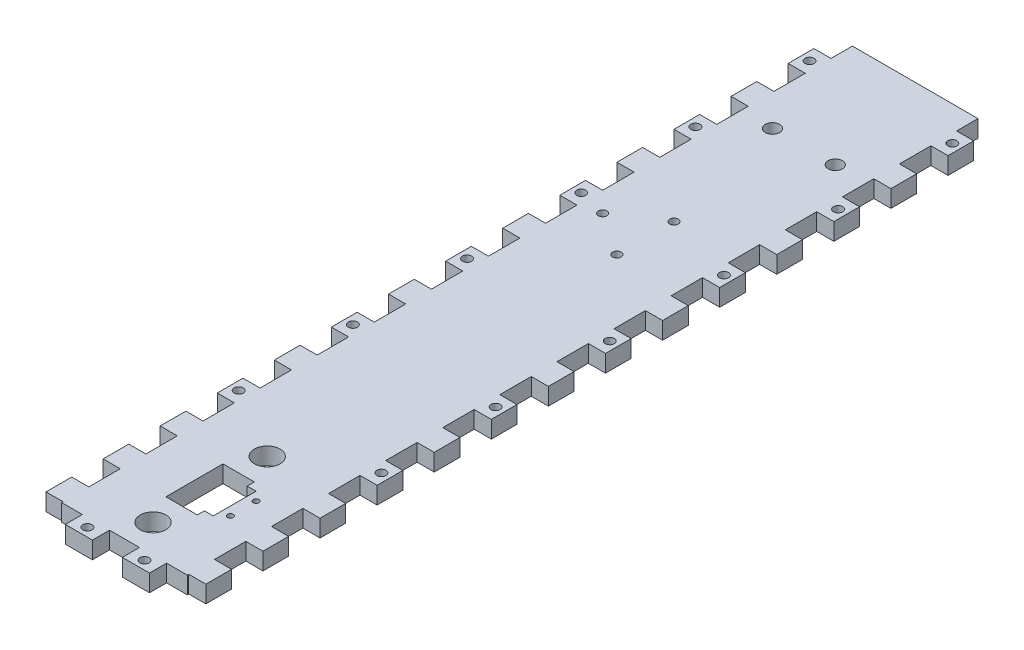
SolidWorks part; units mm, degrees
ref_plane "Plan de face" through (0, 0, 0) normal (0, 0, 1) x (1, 0, 0)
ref_plane "Plan de dessus" through (0, 0, 0) normal (0, 1, 0) x (1, 0, 0)
ref_plane "Plan de droite" through (0, 0, 0) normal (1, 0, 0) x (0, 0, -1)
sketch "Sketch1" plane through (0, 0, 0) normal (0, 0, 1) x (1, 0, 0)
  line L1 (-30.0201, 10.5217) -> (13.9799, 10.5217)
  line L2 (-30.0201, 10.5217) -> (-30.0201, 4.5217)
  line L3 (-30.0201, 4.5217) -> (13.9799, 4.5217)
  line L4 (13.9799, 10.5217) -> (13.9799, 4.5217)
  dimension "D1" = 44
  dimension "D2" = 6
extrude "Boss-Extrude1" add sketch "Sketch1" along normal blind 277
sketch "Sketch4" plane through (13.9799, 0, 0) normal (1, 0, 0) x (0, 0, -1)
  line L0 (-277, 10.5217) -> (0, 10.5217) construction
  line L1 (-276.5, 10.5217) -> (-267.5, 10.5217)
  line L2 (-276.5, 10.5217) -> (-276.5, 4.5217)
  line L3 (-276.5, 4.5217) -> (-267.5, 4.5217)
  line L4 (-267.5, 10.5217) -> (-267.5, 4.5217)
  line L5 (-277, 4.5217) -> (0, 4.5217) construction
  line L6 (-277, 4.5217) -> (-277, 10.5217) construction
  line L7 (-256.5, 10.5217) -> (-256.5, 4.5217)
  line L8 (-256.5, 10.5217) -> (-247.5, 10.5217)
  line L9 (-247.5, 10.5217) -> (-247.5, 4.5217)
  line L10 (-256.5, 4.5217) -> (-247.5, 4.5217)
  line L11 (-236.5, 10.5217) -> (-236.5, 4.5217)
  line L12 (-236.5, 10.5217) -> (-227.5, 10.5217)
  line L13 (-227.5, 10.5217) -> (-227.5, 4.5217)
  line L14 (-236.5, 4.5217) -> (-227.5, 4.5217)
  line L15 (-216.5, 10.5217) -> (-216.5, 4.5217)
  line L16 (-216.5, 10.5217) -> (-207.5, 10.5217)
  line L17 (-207.5, 10.5217) -> (-207.5, 4.5217)
  line L18 (-216.5, 4.5217) -> (-207.5, 4.5217)
  line L19 (-196.5, 10.5217) -> (-196.5, 4.5217)
  line L20 (-196.5, 10.5217) -> (-187.5, 10.5217)
  line L21 (-187.5, 10.5217) -> (-187.5, 4.5217)
  line L22 (-196.5, 4.5217) -> (-187.5, 4.5217)
  line L23 (-176.5, 10.5217) -> (-176.5, 4.5217)
  line L24 (-176.5, 10.5217) -> (-167.5, 10.5217)
  line L25 (-167.5, 10.5217) -> (-167.5, 4.5217)
  line L26 (-176.5, 4.5217) -> (-167.5, 4.5217)
  line L27 (-156.5, 10.5217) -> (-156.5, 4.5217)
  line L28 (-156.5, 10.5217) -> (-147.5, 10.5217)
  line L29 (-147.5, 10.5217) -> (-147.5, 4.5217)
  line L30 (-156.5, 4.5217) -> (-147.5, 4.5217)
  line L31 (-136.5, 10.5217) -> (-136.5, 4.5217)
  line L32 (-136.5, 10.5217) -> (-127.5, 10.5217)
  line L33 (-127.5, 10.5217) -> (-127.5, 4.5217)
  line L34 (-136.5, 4.5217) -> (-127.5, 4.5217)
  line L35 (-116.5, 10.5217) -> (-116.5, 4.5217)
  line L36 (-116.5, 10.5217) -> (-107.5, 10.5217)
  line L37 (-107.5, 10.5217) -> (-107.5, 4.5217)
  line L38 (-116.5, 4.5217) -> (-107.5, 4.5217)
  line L39 (-96.5, 10.5217) -> (-96.5, 4.5217)
  line L40 (-96.5, 10.5217) -> (-87.5, 10.5217)
  line L41 (-87.5, 10.5217) -> (-87.5, 4.5217)
  line L42 (-96.5, 4.5217) -> (-87.5, 4.5217)
  line L43 (-76.5, 10.5217) -> (-76.5, 4.5217)
  line L44 (-76.5, 10.5217) -> (-67.5, 10.5217)
  line L45 (-67.5, 10.5217) -> (-67.5, 4.5217)
  line L46 (-76.5, 4.5217) -> (-67.5, 4.5217)
  line L47 (-56.5, 10.5217) -> (-56.5, 4.5217)
  line L48 (-56.5, 10.5217) -> (-47.5, 10.5217)
  line L49 (-47.5, 10.5217) -> (-47.5, 4.5217)
  line L50 (-56.5, 4.5217) -> (-47.5, 4.5217)
  line L51 (-36.5, 10.5217) -> (-36.5, 4.5217)
  line L52 (-36.5, 10.5217) -> (-27.5, 10.5217)
  line L53 (-27.5, 10.5217) -> (-27.5, 4.5217)
  line L54 (-36.5, 4.5217) -> (-27.5, 4.5217)
  line L55 (-16.5, 10.5217) -> (-16.5, 4.5217)
  line L56 (-16.5, 10.5217) -> (-7.5, 10.5217)
  line L57 (-7.5, 10.5217) -> (-7.5, 4.5217)
  line L58 (-16.5, 4.5217) -> (-7.5, 4.5217)
  dimension "D1" = 0.5
  dimension "D2" = 9
  dimension "D3" = 14
extrude "Boss-Extrude2" add sketch "Sketch4" along normal blind 6
sketch "Sketch5" plane through (-30.0201, 0, 0) normal (-1, 0, 0) x (0, 0, 1)
  line L0 (277, 4.5217) -> (0, 4.5217) construction
  line L1 (276.5, 4.5217) -> (267.5, 4.5217)
  line L2 (276.5, 4.5217) -> (276.5, 10.5217)
  line L3 (276.5, 10.5217) -> (267.5, 10.5217)
  line L4 (267.5, 4.5217) -> (267.5, 10.5217)
  line L5 (277, 10.5217) -> (0, 10.5217) construction
  line L6 (277, 10.5217) -> (277, 4.5217) construction
  line L7 (256.5, 4.5217) -> (256.5, 10.5217)
  line L8 (256.5, 4.5217) -> (247.5, 4.5217)
  line L9 (247.5, 4.5217) -> (247.5, 10.5217)
  line L10 (256.5, 10.5217) -> (247.5, 10.5217)
  line L11 (236.5, 4.5217) -> (236.5, 10.5217)
  line L12 (236.5, 4.5217) -> (227.5, 4.5217)
  line L13 (227.5, 4.5217) -> (227.5, 10.5217)
  line L14 (236.5, 10.5217) -> (227.5, 10.5217)
  line L15 (216.5, 4.5217) -> (216.5, 10.5217)
  line L16 (216.5, 4.5217) -> (207.5, 4.5217)
  line L17 (207.5, 4.5217) -> (207.5, 10.5217)
  line L18 (216.5, 10.5217) -> (207.5, 10.5217)
  line L19 (196.5, 4.5217) -> (196.5, 10.5217)
  line L20 (196.5, 4.5217) -> (187.5, 4.5217)
  line L21 (187.5, 4.5217) -> (187.5, 10.5217)
  line L22 (196.5, 10.5217) -> (187.5, 10.5217)
  line L23 (176.5, 4.5217) -> (176.5, 10.5217)
  line L24 (176.5, 4.5217) -> (167.5, 4.5217)
  line L25 (167.5, 4.5217) -> (167.5, 10.5217)
  line L26 (176.5, 10.5217) -> (167.5, 10.5217)
  line L27 (156.5, 4.5217) -> (156.5, 10.5217)
  line L28 (156.5, 4.5217) -> (147.5, 4.5217)
  line L29 (147.5, 4.5217) -> (147.5, 10.5217)
  line L30 (156.5, 10.5217) -> (147.5, 10.5217)
  line L31 (136.5, 4.5217) -> (136.5, 10.5217)
  line L32 (136.5, 4.5217) -> (127.5, 4.5217)
  line L33 (127.5, 4.5217) -> (127.5, 10.5217)
  line L34 (136.5, 10.5217) -> (127.5, 10.5217)
  line L35 (116.5, 4.5217) -> (116.5, 10.5217)
  line L36 (116.5, 4.5217) -> (107.5, 4.5217)
  line L37 (107.5, 4.5217) -> (107.5, 10.5217)
  line L38 (116.5, 10.5217) -> (107.5, 10.5217)
  line L39 (96.5, 4.5217) -> (96.5, 10.5217)
  line L40 (96.5, 4.5217) -> (87.5, 4.5217)
  line L41 (87.5, 4.5217) -> (87.5, 10.5217)
  line L42 (96.5, 10.5217) -> (87.5, 10.5217)
  line L43 (76.5, 4.5217) -> (76.5, 10.5217)
  line L44 (76.5, 4.5217) -> (67.5, 4.5217)
  line L45 (67.5, 4.5217) -> (67.5, 10.5217)
  line L46 (76.5, 10.5217) -> (67.5, 10.5217)
  line L47 (56.5, 4.5217) -> (56.5, 10.5217)
  line L48 (56.5, 4.5217) -> (47.5, 4.5217)
  line L49 (47.5, 4.5217) -> (47.5, 10.5217)
  line L50 (56.5, 10.5217) -> (47.5, 10.5217)
  line L51 (36.5, 4.5217) -> (36.5, 10.5217)
  line L52 (36.5, 4.5217) -> (27.5, 4.5217)
  line L53 (27.5, 4.5217) -> (27.5, 10.5217)
  line L54 (36.5, 10.5217) -> (27.5, 10.5217)
  line L55 (16.5, 4.5217) -> (16.5, 10.5217)
  line L56 (16.5, 4.5217) -> (7.5, 4.5217)
  line L57 (7.5, 4.5217) -> (7.5, 10.5217)
  line L58 (16.5, 10.5217) -> (7.5, 10.5217)
  dimension "D1" = 0.5
  dimension "D2" = 9
  dimension "D3" = 14
extrude "Boss-Extrude3" add sketch "Sketch5" along normal blind 6
sketch "Sketch6" plane through (0, 0, 277) normal (0, 0, 1) x (1, 0, 0)
  line L0 (13.9799, 10.5217) -> (-30.0201, 10.5217) construction
  line L1 (-22.7701, 10.5217) -> (-13.2701, 10.5217)
  line L2 (-22.7701, 10.5217) -> (-22.7701, 4.5217)
  line L3 (-22.7701, 4.5217) -> (-13.2701, 4.5217)
  line L4 (-13.2701, 10.5217) -> (-13.2701, 4.5217)
  line L5 (-30.0201, 4.5217) -> (13.9799, 4.5217) construction
  line L6 (-30.0201, 4.5217) -> (-30.0201, 10.5217) construction
  line L7 (-2.7701, 10.5217) -> (-2.7701, 4.5217)
  line L8 (-2.7701, 10.5217) -> (6.7299, 10.5217)
  line L9 (6.7299, 10.5217) -> (6.7299, 4.5217)
  line L10 (-2.7701, 4.5217) -> (6.7299, 4.5217)
  dimension "D1" = 7.25
  dimension "D2" = 9.5
  dimension "D3" = 2
extrude "Boss-Extrude4" add sketch "Sketch6" along normal blind 6
sketch "Sketch7" plane through (0, 4.5217, 0) normal (0, -1, 0) x (1, 0, 0)
  line L0 (-8.0201, 277) -> (-8.0201, 0) construction
  line L2 (-30.0201, 0) -> (13.9799, 0) construction
  line L3 (19.9799, 256.5) -> (19.9799, 247.5) construction
  line L6 (19.9799, 256.5) -> (13.9799, 256.5) construction
  circle A0 centre (16.9799, 252) radius 1.6
  circle A1 centre (-33.0201, 252) radius 1.6
  circle A2 centre (-33.0201, 212) radius 1.6
  circle A3 centre (16.9799, 212) radius 1.6
  circle A4 centre (-33.0201, 172) radius 1.6
  circle A5 centre (16.9799, 172) radius 1.6
  circle A6 centre (-33.0201, 132) radius 1.6
  circle A7 centre (16.9799, 132) radius 1.6
  circle A8 centre (-33.0201, 92) radius 1.6
  circle A9 centre (16.9799, 92) radius 1.6
  circle A10 centre (-33.0201, 52) radius 1.6
  circle A11 centre (16.9799, 52) radius 1.6
  circle A12 centre (-33.0201, 12) radius 1.6
  circle A13 centre (16.9799, 12) radius 1.6
  point P6 (19.9799, 252)
  point P15 (16.9799, 256.5)
  dimension "D1" = 7
  dimension "D3" = 3.2
extrude "Cut-Extrude1" cut sketch "Sketch7" against normal through all
sketch "Sketch8" plane through (0, 4.5217, 0) normal (0, -1, 0) x (1, 0, 0)
  line L0 (-8.0201, 0) -> (-8.0201, 54.5316) construction
  line L1 (-30.0201, 0) -> (13.9799, 0) construction
  circle A0 centre (-19.0201, 39) radius 2.5
  circle A1 centre (2.9799, 39) radius 2.5
  dimension "D1" = 5
  dimension "D2" = 11
  dimension "D3" = 39
extrude "Cut-Extrude2" cut sketch "Sketch8" against normal blind 12
sketch "Sketch9" plane through (0, 4.5217, 0) normal (0, -1, 0) x (-1, 0, 0)
  line L1 (2.7701, -283) -> (-6.7299, -283) construction
  line L2 (22.7701, -283) -> (13.2701, -283) construction
  line L3 (13.2701, -283) -> (13.2701, -277) construction
  line L4 (-6.7299, -283) -> (-6.7299, -277) construction
  circle A0 centre (18.0201, -280) radius 1.6
  circle A1 centre (-1.9799, -280) radius 1.6
  point P2 (-1.9799, -283)
  point P6 (18.0201, -283)
  point P14 (13.2701, -280)
  point P17 (-6.7299, -280)
  dimension "D1" = 3.2
  dimension "D2" = 3.2
extrude "Cut-Extrude3" cut sketch "Sketch9" against normal blind 12
sketch "Sketch11" plane through (0, 4.5217, 0) normal (0, -1, 0) x (1, 0, 0)
  line L0 (6.7299, 277) -> (13.9799, 277) construction
  line L2 (-13.5201, 257) -> (-2.5201, 257)
  line L3 (-13.5201, 257) -> (-13.5201, 237)
  line L4 (-13.5201, 237) -> (-2.5201, 237)
  line L5 (-2.5201, 257) -> (-2.5201, 237)
  line L6 (-2.5201, 254.5) -> (0.5799, 254.5)
  line L7 (-2.5201, 254.5) -> (-2.5201, 239.5)
  line L8 (-2.5201, 239.5) -> (0.5799, 239.5)
  line L9 (0.5799, 254.5) -> (0.5799, 239.5)
  line L10 (-13.2701, 277) -> (-2.7701, 277) construction
  circle A0 centre (-8.0201, 267) radius 4.5
  circle A1 centre (-8.0201, 227) radius 4.5
  circle A2 centre (3.5799, 251.5) radius 1
  circle A3 centre (3.5799, 242.5) radius 1
  point P11 (-8.0201, 257)
  point P16 (-2.5201, 247)
  point P17 (-2.5201, 247)
  point P24 (-8.0201, 277)
  dimension "D1" = 9
  dimension "D2" = 9
  dimension "D10" = 2
  dimension "D11" = 2
  dimension "D3" = 40
  dimension "D4" = 10
  dimension "D5" = 11
  dimension "D6" = 10
  dimension "D7" = 10
  dimension "D8" = 3.1
  dimension "D9" = 15
  dimension "D12" = 3
  dimension "D13" = 3
  dimension "D14" = 3
extrude "Cut-Extrude4" cut sketch "Sketch11" against normal through all contours L5 L2 L3 L4 | L9 L6 L5 L8 | A0 | A1 | A2 | A3 region at (-8.0201, 4.5217, 247) region at (-0.9701, 4.5217, 247) region at (-8.0201, 4.5217, 267) region at (-8.0201, 4.5217, 227) region at (3.5799, 4.5217, 251.5) region at (3.5799, 4.5217, 242.5)
extrude "Boss-Extrude5" add sketch "Sketch7<2>" against normal through all contours A1 | A0 region at (16.9799, 4.5217, 252) region at (-33.0201, 4.5217, 252)
sketch "Sketch7<2>" plane through (0, 4.5217, 0) normal (0, -1, 0) x (1, 0, 0) same geometry as "Sketch7"
sketch "Sketch12" plane through (0, 10.5217, 0) normal (0, 1, 0) x (1, 0, 0)
  line L1 (13.9799, 0) -> (-30.0201, 0) construction
  line L2 (-13.2701, -277) -> (-2.7701, -277) construction
  circle A0 centre (-8.0201, -104.5) radius 1.5
  circle A1 centre (-8.0201, -84.5) radius 1.5
  circle A2 centre (-23.0201, -94.5) radius 1.5
  point P14 (-8.0201, 0)
  dimension "D1" = 3
  dimension "D2" = 3
  dimension "D3" = 3
  dimension "D4" = 15
  dimension "D5" = 10
  dimension "D6" = 10
  dimension "D7" = 172.5
extrude "Cut-Extrude5" cut sketch "Sketch12" against normal through all both and the other way through all
equation "\"3.é\"=2.2"
